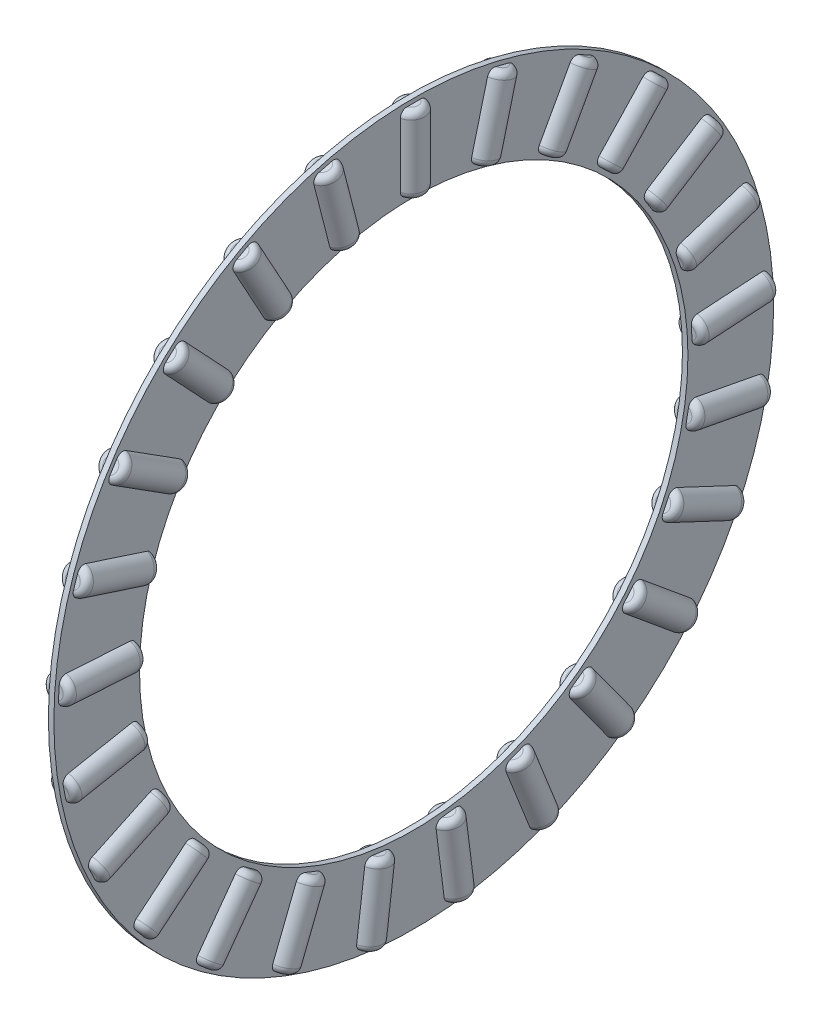
SolidWorks part; units mm, degrees
ref_plane "Plane1" through (0, 0, 0) normal (0, 0, 1) x (1, 0, 0)
ref_plane "Plane2" through (0, 0, 0) normal (0, 1, 0) x (1, 0, 0)
ref_plane "Plane3" through (0, 0, 0) normal (1, 0, 0) x (0, 0, -1)
sketch "Clipboard" plane through (0, 0, 0) normal (0, 0, 1) x (1, 0, 0)
  line L0 (-10, 0) -> (10, 0) construction
  line L1 (0, 0) -> (20.2657, -9.45)
  line L2 (0, 0) -> (41.9167, 19.5461)
  line L3 (0, 0) -> (20.2657, -9.45)
  line L4 (0, 0) -> (-22.3471, -0.7804)
  dimension "BallCLRad" = 46.25
sketch "CagSpiSke" plane through (0, 0, 0) normal (0, 0, 1) x (1, 0, 0)
  line L5 (-34.925, 0) -> (34.925, 0) construction
  line L6 (-0.4, 52.5) -> (0.4, 52.5)
  line L7 (-0.4, 52.5) -> (-0.4, 40)
  line L8 (-0.4, 40) -> (0.4, 40)
  line L9 (0.4, 52.5) -> (0.4, 40)
  dimension "ID" = 80
  dimension "OD" = 105
revolve "CageSpine" add sketch "CagSpiSke" angle 360 about L5 reverse direction yes
ref_axis "Axis1" through (-50, 0, 0) along (1, 0, 0)
sketch "RolDetSke" plane through (0, 0, 0) normal (0, 0, 1) x (1, 0, 0)
  line L0 (0, 33.02) -> (0, 55.88) construction
  line L3 (0, 51.875) -> (1.04, 51.875)
  line L4 (0, 51.875) -> (0, 40.625)
  line L5 (0, 40.625) -> (1.04, 40.625)
  line L6 (2, 50.915) -> (2, 41.585)
  arc A0 (2, 41.585) -> (1.04, 40.625) centre (1.04, 41.585) cw
  arc A1 (1.04, 51.875) -> (2, 50.915) centre (1.04, 50.915) cw
  dimension "offset" = 40.625
  dimension "Roller_diameter" = 4
  dimension "Cyl_Len" = 11.25
revolve "RollerDetailed" add sketch "RolDetSke" angle 360 about L0 reverse direction yes
pattern_circular "RollersDetailed" count 25 every 14.4 about axis through (-50, 0, 0) along (1, 0, 0) of "RollerDetailed"
sketch "RolSimSke" plane through (0, 0, 0) normal (0, 0, 1) x (1, 0, 0)
  line L1 (-17.78, 0) -> (12.7, 0) construction
  line L3 (-1.04, 51.875) -> (1.04, 51.875)
  line L4 (-2, 50.915) -> (-2, 41.585)
  line L5 (-1.04, 40.625) -> (1.04, 40.625)
  line L6 (2, 50.915) -> (2, 41.585)
  arc A0 (-2, 41.585) -> (-1.04, 40.625) centre (-1.04, 41.585) ccw
  arc A1 (-1.04, 51.875) -> (-2, 50.915) centre (-1.04, 50.915) ccw
  arc A2 (2, 50.915) -> (1.04, 51.875) centre (1.04, 50.915) ccw
  arc A3 (1.04, 40.625) -> (2, 41.585) centre (1.04, 41.585) ccw
  dimension "Halfdia" = 2
  dimension "offset" = 40.625
  dimension "Roller_diameter" = 4
  dimension "Cyl_Len" = 11.25
revolve "RollersSimplified" [suppressed] add sketch "RolSimSke" angle 360 about L1
equation "\"BallCLRad@Clipboard\" =  ( \"OD@CagSpiSke\" + \"ID@CagSpiSke\" )  / 4"
equation "\"offset@RolSimSke\" = \"BallCLRad@Clipboard\" - \"Cyl_Len@RolSimSke\" / 2"
equation "\"offset@RolDetSke\" = \"BallCLRad@Clipboard\" - \"Cyl_Len@RolDetSke\" / 2"
equation "\"Thickness@CagSpiSke\" =  \"Roller_diameter@RolDetSke\" * 0.2"
equation "\"HalfThick@CagSpiSke\" = \"Thickness@CagSpiSke\" / 2"
equation "\"radius@RolDetSke\" =  ( \"Roller_diameter@RolDetSke\" - \"Thickness@CagSpiSke\" )  * 0.6 / 2"
equation "\"Roller_diameter@RolSimSke\" = \"Roller_diameter@RolDetSke\""
equation "\"Cyl_Len@RolSimSke\" = \"Cyl_Len@RolDetSke\""
equation "\"Rol_rad@RolSimSke\" = \"radius@RolDetSke\""
equation "\"Halfdia@RolSimSke\" = \"Roller_diameter@RolSimSke\" / 2"
equation "\"Max_count@Clipboard\" = int( 3.14159265 / atn(( \"Roller_diameter@RolDetSke\" / 2) / sqr( \"offset@RolDetSke\"  *  \"offset@RolDetSke\" - ( \"Roller_diameter@RolDetSke\" / 2) *  ( \"Roller_diameter@RolDetSke\" / 2))))"
equation "\"Max_count@Clipboard\" = ((sgn( \"Max_count@Clipboard\" - \"Count@Clipboard\" )-1)*( \"Max_count@Clipboard\" - \"Count@Clipboard\" ))/-2+ \"Count@Clipboard\""
equation "\"Count@RollersDetailed\" = int( \"Show_count@Clipboard\" ) "
equation "\"Count@RollersDetailed\" = ((sgn( \"Count@RollersDetailed\" - \"Max_count@Clipboard\" )-1)*( \"Count@RollersDetailed\" - \"Max_count@Clipboard\" ))/-2+ \"Max_count@Clipboard\""
equation "\"Count@RollersDetailed\" = ((sgn( \"Count@RollersDetailed\" - \"Min_count@Clipboard\" )+1)*( \"Count@RollersDetailed\" - \"Min_count@Clipboard\"))/2 +\"Min_count@Clipboard\""
equation "\"Angle@RollersDetailed\" = 360.0 / \"Max_count@Clipboard\""
